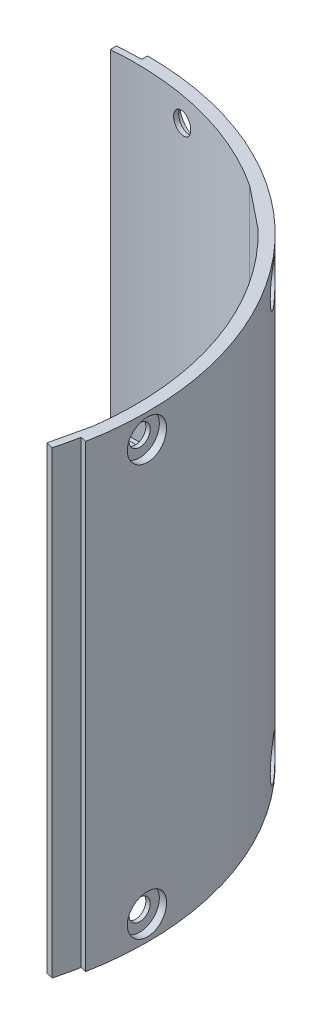
SolidWorks part; units mm, degrees
ref_plane "Спереди" through (0, 0, 0) normal (0, 0, 1) x (1, 0, 0)
ref_plane "Сверху" through (0, 0, 0) normal (0, 1, 0) x (1, 0, 0)
ref_plane "Справа" through (0, 0, 0) normal (1, 0, 0) x (0, 0, -1)
sketch "Эскиз2" plane through (0, 0, 0) normal (0, 1, 0) x (1, 0, 0)
  line L0 (0, -1000) -> (0, 49000) construction
  line L1 (-8.2529, 48.3) -> (8.2529, 48.3) construction
  line L2 (33.9524, 35.3303) -> (27.0476, 40.8587) construction
  line L3 (48.5627, -6.5315) -> (46.5973, -15.1557) construction
  line L4 (-3.9968, 48.3) -> (8.2529, 48.3)
  line L5 (33.9524, 35.3303) -> (27.0476, 40.8587)
  line L6 (48.5627, -6.5315) -> (46.5973, -15.1557) construction
  line L7 (-3.9968, 48.3) -> (-3.9968, 49.84)
  line L10 (-8.2529, 48.3) -> (-3.9968, 48.3) construction
  line L11 (0, 50) -> (0, 51)
  line L12 (0, 0) -> (47.58, -10.8436) construction
  line L16 (47.58, -10.8436) -> (49.725, -11.3324) construction
  line L17 (47.1356, -12.7936) -> (48.5627, -6.5315)
  line L19 (47.1356, -12.7936) -> (48.2666, -13.0514)
  line L20 (50.1312, -9.3737) -> (49.1554, -9.1514)
  circle A0 centre (0, 0) radius 51 construction
  arc A1 (50.1312, -9.3737) -> (0, 51) centre (0, 0) ccw
  circle A2 centre (0, 0) radius 51 construction
  arc A3 (48.5627, -6.5315) -> (33.9524, 35.3303) centre (0, 0) ccw construction
  arc A4 (0, 51) -> (0, -51) centre (0, 0) ccw construction
  arc A5 (48.5627, -6.5315) -> (33.9524, 35.3303) centre (0, 0) ccw
  arc A6 (8.2529, 48.3) -> (27.0476, 40.8587) centre (0, 0) cw
  arc A7 (0, -51) -> (49.725, -11.3324) centre (0, 0) ccw construction
  arc A8 (49.725, -11.3324) -> (50.1312, -9.3737) centre (0, 0) ccw construction
  arc A9 (0, 50) -> (-3.9968, 49.84) centre (0, 0) ccw
  arc A10 (49.1554, -9.1514) -> (48.2666, -13.0514) centre (0, 0) cw
  dimension "D1" = 3.9968
  dimension "D2" = 1
  dimension "D3" = 4
extrude "Бобышка-Вытянуть2" add sketch "Эскиз2" along normal up to surface (76 mm away)
ref_plane "Плоскость4" through (12.7171, 0, -36.1271) normal (-0.332, 0, 0.9433) x (0.9433, 0, 0.332)
sketch "Эскиз7" plane through (12.7171, 0, -36.1271) normal (-0.332, 0, 0.9433) x (0.9433, 0, 0.332)
  line L5 (-8.2529, 17) -> (5.2529, 17) construction
  line L6 (-8.2529, 17) -> (5.2529, 17) construction
  line L7 (8.2529, 14) -> (5.2529, 17) construction
  line L8 (8.2529, 14) -> (5.2529, 17)
  line L9 (-8.2529, 0) -> (8.2529, 0) construction
  line L16 (-8.2529, 0) -> (8.2529, 0)
  line L17 (-8.2529, 76) -> (-8.2529, 0) construction
  line L18 (-8.2529, 17) -> (-8.2529, 0) construction
  line L19 (8.7529, 14.2071) -> (8.7529, 0)
  line L20 (8.7529, 14.2071) -> (5.46, 17.5)
  line L21 (8.2529, 14) -> (8.2529, 0) construction
  line L22 (8.2529, 14) -> (8.2529, 0) construction
  line L23 (-8.7529, 17.5) -> (5.46, 17.5)
  line L24 (-8.7529, 17.5) -> (-8.7529, 0)
  line L25 (-8.7529, 0) -> (-8.2529, 0)
  line L26 (8.2529, 0) -> (8.7529, 0)
  dimension "D1" = 0.5
extrude "Вырез-Вытянуть3" cut sketch "Эскиз7" against normal through all contours L16 L26 L19 L20 L23 L24 L25 region at (12.587, 8.6121, -36.1729)
sketch "Эскиз9" plane through (0, 0, -48.3) normal (0, 0, 1) x (1, 0, 0)
  line L4 (8.7529, 0) -> (8.7529, 17.5)
  line L6 (-3.9968, 76) -> (-3.9968, 0) construction
  line L7 (-3.9968, 19.5032) -> (-3.9968, 0)
  line L8 (-3.9968, 76) -> (-3.9968, 19.5032) construction
  line L9 (-3.9968, 19.5032) -> (-6.5, 17) construction
  line L10 (-8.2529, 0) -> (-3.9968, 0) construction
  line L11 (8.7529, 17.5) -> (6.7071, 17.5)
  line L12 (6.7071, 17.5) -> (3.7071, 20.5)
  line L13 (3.7071, 20.5) -> (-3.7071, 20.5)
  line L14 (-8.2529, 0) -> (8.2529, 0)
  line L15 (8.2529, 0) -> (8.2529, 17)
  line L24 (8.2529, 17) -> (6.5, 17)
  line L25 (6.5, 17) -> (3.5, 20)
  line L26 (3.5, 20) -> (-3.5, 20)
  line L28 (-3.7071, 20.5) -> (-3.9968, 20.2104)
  line L29 (-3.5, 20) -> (-6.5, 17)
  line L30 (-6.5, 17) -> (-8.2529, 17)
  line L31 (-8.2529, 17) -> (-8.2529, 0)
  line L32 (-3.9968, 0) -> (8.2529, 0)
  line L33 (8.2529, 0) -> (8.2529, 17) construction
  line L34 (8.2529, 17) -> (6.5, 17) construction
  line L35 (6.5, 17) -> (3.5, 20) construction
  line L36 (3.5, 20) -> (-3.5, 20) construction
  line L37 (-3.5, 20) -> (-3.9968, 19.5032)
  line L38 (-6.5, 17) -> (-8.2529, 17) construction
  line L39 (-8.2529, 17) -> (-8.2529, 0) construction
  line L40 (-3.9968, 19.5032) -> (-3.9968, 20.2104)
  line L41 (-3.9968, 20.2104) -> (-4.3503, 19.8568) construction
  line L42 (-3.7071, 20.5) -> (-4.3503, 19.8568) construction
  line L43 (8.7529, 0) -> (8.2529, 0)
  line M9 (-8.2529, 0) -> (8.2529, 0)
  line M10 (8.2529, 0) -> (8.2529, 17)
  line M11 (8.2529, 17) -> (6.5, 17)
  line M12 (6.5, 17) -> (3.5, 20)
  line M13 (3.5, 20) -> (-3.5, 20)
  line M14 (-3.5, 20) -> (-6.5, 17)
  dimension "D1" = 0
  dimension "D2" = 0.5
extrude "Вырез-Вытянуть4" cut sketch "Эскиз9" against normal through all contours L7 M14 M9 M10 M11 M12 M13 | L43 L4 L11 L12 L13 L28 L40 M14 M13 M12 M11 M10 region at (8.5029, 0.2414, -48.3) region at (1.9493, 9.6325, -48.3)
sketch "Эскиз10" plane through (0, 12, 0) normal (0, 1, 0) x (1, 0, 0)
  line L0 (-3.9968, 48.3) -> (8.2529, 48.3) construction
  line L1 (-3.9968, 48.3) -> (8.2529, 48.3)
  line L2 (23.8222, 42.8194) -> (20.9924, 43.8155) construction
  line L3 (8.2529, 48.3) -> (20.9924, 43.8155) construction
  line L4 (23.8222, 42.8194) -> (20.9924, 43.8155)
  line L5 (8.2529, 48.3) -> (20.9924, 43.8155)
  line L7 (23.4097, 41.9045) -> (20.6603, 42.8723)
  line L8 (8.082, 47.3) -> (20.6603, 42.8723)
  line L9 (-3.9968, 47.3) -> (8.082, 47.3)
  line L10 (-3.9968, 47.3) -> (-3.9968, 48.3)
  line L11 (26.4956, 40.0248) -> (27.0476, 40.8587) construction
  line L12 (26.4956, 40.0248) -> (28.4646, 39.7241)
  line L13 (27.0476, 40.8587) -> (33.9524, 35.3303) construction
  line L14 (28.4646, 39.7241) -> (27.0476, 40.8587) construction
  line L15 (28.4646, 39.7241) -> (27.0476, 40.8587) construction
  line L16 (28.4646, 39.7241) -> (27.0476, 40.8587)
  arc A0 (27.0476, 40.8587) -> (8.2529, 48.3) centre (0, 0) ccw construction
  arc A1 (27.0476, 40.8587) -> (23.8222, 42.8194) centre (0, 0) ccw
  arc A2 (23.8222, 42.8194) -> (8.2529, 48.3) centre (0, 0) ccw construction
  arc A3 (26.4956, 40.0248) -> (23.4097, 41.9045) centre (0, 0) ccw
  dimension "D2" = 30
  dimension "D1" = 1
extrude "Бобышка-Вытянуть7" add sketch "Эскиз10" along normal blind 10
sketch "Эскиз13" plane through (0, 22, 0) normal (0, 1, 0) x (1, 0, 0)
  line L0 (23.8222, 42.8194) -> (8.2529, 48.3) construction
  line L1 (23.8222, 42.8194) -> (8.2529, 48.3)
  arc A0 (27.0476, 40.8587) -> (8.2529, 48.3) centre (0, 0) ccw construction
  arc A1 (27.0476, 40.8587) -> (8.2529, 48.3) centre (0, 0) ccw
  line M2 (23.8222, 42.8194) -> (8.2529, 48.3)
extrude "Бобышка-Вытянуть8" add sketch "Эскиз13" against normal up to surface (4.5 mm away) contours A1 M2 region at (16.1306, 22, -45.824) up to face at (13.0597, 17.5, -47.6707)
sketch "Эскиз14" plane through (0, 17.5, 0) normal (0, -1, 0) x (1, 0, 0)
  line L0 (21.3189, -44.1192) -> (21.1877, -43.7468)
  line L1 (21.1877, -43.7468) -> (8.2529, -48.3) construction
  line L4 (21.9869, -46.0171) -> (21.3189, -44.1192)
  line L5 (23.8222, -42.8194) -> (8.2529, -48.3)
  line L6 (8.2529, -48.3) -> (6.7071, -48.3)
  line L7 (6.7071, -48.3) -> (6.7071, -50.557)
  line L8 (21.9869, -46.0171) -> (21.3189, -44.1192)
  line L9 (23.8222, -42.8194) -> (21.1877, -43.7468)
  line L10 (8.2529, -48.3) -> (6.7071, -48.3) construction
  line L11 (6.7071, -48.3) -> (6.7071, -50.557) construction
  arc A2 (6.7071, -50.557) -> (21.9869, -46.0171) centre (0, 0) ccw
  arc A3 (21.3189, -44.1192) -> (23.8222, -42.8194) centre (0, 0) ccw
  arc A4 (6.7071, -50.557) -> (21.9869, -46.0171) centre (0, 0) ccw construction
  arc A5 (21.3189, -44.1192) -> (23.8222, -42.8194) centre (0, 0) ccw
  dimension "D1" = 0
extrude "Бобышка-Вытянуть9" add sketch "Эскиз14" along normal up to surface contours A5 L9 L0 up to face at (23.2708, 15.6229, -44.011)
chamfer "Фаска1" distance 1 angle 45 4 edges at (2.0426, 22, -47.3) (15.7459, 22, -44.6022) (24.9703, 22, -40.9937) (27.4801, 22, -39.8745)
ref_plane "Плоскость5" through (51, 0, 0) normal (1, 0, 0) x (0, 0, -1)
sketch "Эскиз15" plane through (51, 0, 0) normal (1, 0, 0) x (0, 0, -1)
  line L0 (0, -1000) -> (0, 49000) construction
  circle A0 centre (0, 4) radius 3.25
  dimension "D1" = 6.5
  dimension "D2" = 4
extrude "Вырез-Вытянуть5" cut sketch "Эскиз15" against normal blind 1.3
sketch "Эскиз16" plane through (49.7, 0, 0) normal (1, 0, 0) x (0, 0, -1)
  circle A0 centre (0, 4) radius 3.25 construction
  circle A1 centre (0, 4) radius 3.25 construction
  circle A2 centre (0, 4) radius 1.75
  dimension "D1" = 3.5
extrude "Вырез-Вытянуть6" cut sketch "Эскиз16" against normal through all
pattern_circular "Круговой массив3" count 3 every 20 about axis through (0, 0, 0) along (0, 1, 0) skipping 1 of "Вырез-Вытянуть5", "Вырез-Вытянуть6"
sketch "Эскиз17" plane through (51, 0, 0) normal (1, 0, 0) x (0, 0, -1)
  line L0 (0, -1000) -> (0, 49000) construction
  line L1 (51, 76) -> (-9.3737, 76) construction
  circle A0 centre (0, 72) radius 3.25
  circle A1 centre (0, 4) radius 3.25 construction
  dimension "D1" = 4
extrude "Вырез-Вытянуть7" cut sketch "Эскиз17" against normal blind 1.3
sketch "Эскиз18" plane through (49.7, 0, 0) normal (1, 0, 0) x (0, 0, -1)
  circle A0 centre (0, 72) radius 3.25 construction
  circle A1 centre (0, 72) radius 3.25 construction
  circle A2 centre (0, 72) radius 1.75
  circle A3 centre (0, 4) radius 1.75 construction
extrude "Вырез-Вытянуть8" cut sketch "Эскиз18" against normal through all
pattern_circular "Круговой массив5" count 5 every 20 about axis through (0, 76, 0) along (0, 1, 0) skipping 1, 3 of "Вырез-Вытянуть8", "Вырез-Вытянуть7"
sketch "Эскиз19" plane through (0, 76, 0) normal (0, 1, 0) x (1, 0, 0)
  line L0 (-3.9968, 49.84) -> (-3.9968, 48.3) construction
  line L1 (8.2529, 48.3) -> (-3.9968, 48.3) construction
  line L2 (8.2529, 48.3) -> (-3.9968, 48.3)
  line L3 (-3.9968, 48.8367) -> (-3.9968, 48.3)
  line L4 (-3.9968, 49.84) -> (-3.9968, 48.8367) construction
  arc A0 (27.0476, 40.8587) -> (8.2529, 48.3) centre (0, 0) ccw construction
  arc A1 (27.0476, 40.8587) -> (8.2529, 48.3) centre (0, 0) ccw construction
  arc A2 (8.2529, 48.3) -> (-3.9968, 48.8367) centre (0, 0) ccw
extrude "Вырез-Вытянуть9" cut sketch "Эскиз19" against normal up to vertex (54 mm away) up to point (-3.9968, 22, -48.3)
